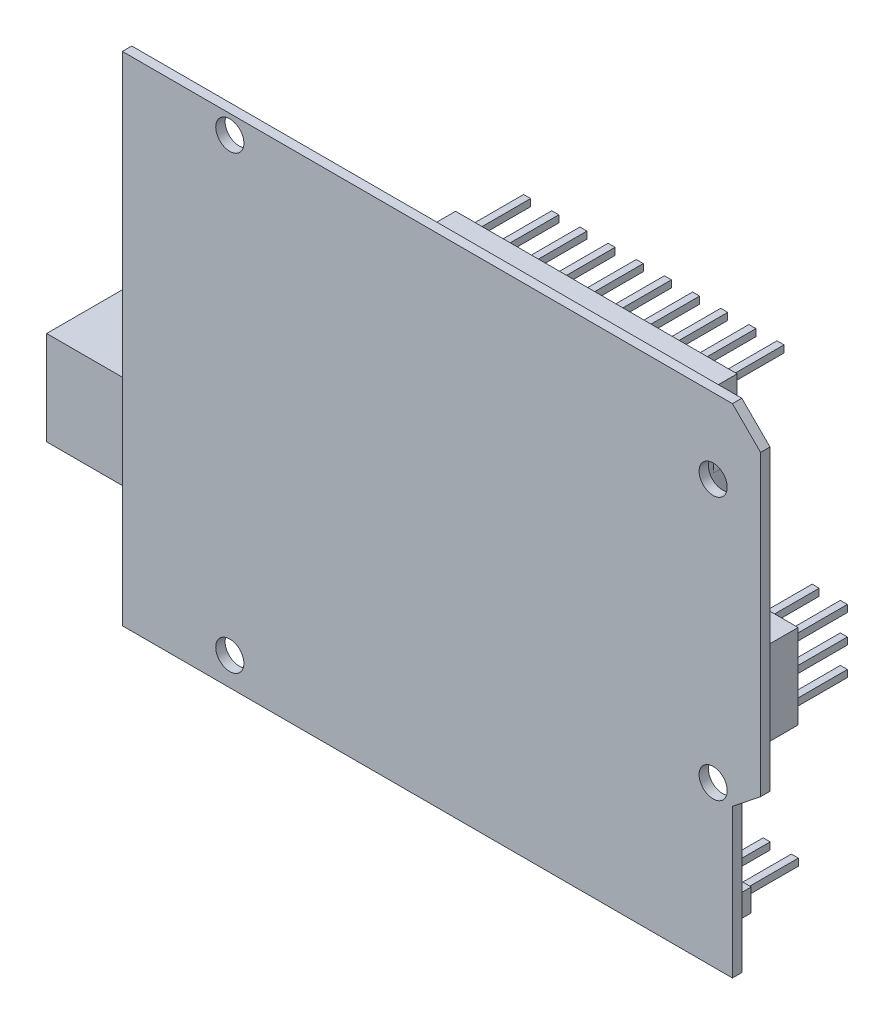
SolidWorks part; units mm, degrees
ref_plane "Front Plane" through (0, 0, 0) normal (0, 0, 1) x (1, 0, 0)
ref_plane "Top Plane" through (0, 0, 0) normal (0, 1, 0) x (1, 0, 0)
ref_plane "Right Plane" through (0, 0, 0) normal (1, 0, 0) x (0, 0, -1)
sketch "Sketch1" plane through (0, 0, 0) normal (0, 0, 1) x (1, 0, 0)
  line L0 (22.754, 124.2709) -> (19.754, 127.2709)
  line L1 (19.754, 74.2709) -> (-45.246, 74.2709)
  line L2 (22.754, 92.5002) -> (22.754, 124.2709)
  line L3 (19.754, 127.2709) -> (-45.246, 127.2709)
  line L4 (-45.246, 74.2709) -> (-45.246, 127.2709)
  line L5 (22.754, 92.5002) -> (19.754, 90.1139)
  line L6 (19.754, 90.1139) -> (19.754, 74.2709)
extrude "Boss-Extrude1" add sketch "Sketch1" against normal blind 1
sketch "Sketch2" plane through (0, 0, -1) normal (0, 0, -1) x (-1, 0, 0)
  line L1 (38.3165, 86.2081) -> (54.3165, 86.2081)
  line L2 (38.3165, 86.2081) -> (38.3165, 96.2081)
  line L3 (38.3165, 96.2081) -> (54.3165, 96.2081)
  line L4 (54.3165, 86.2081) -> (54.3165, 96.2081)
  dimension "D1" = 16
  dimension "D2" = 10
extrude "Boss-Extrude2" add sketch "Sketch2" along normal blind 10
sketch "Sketch3" plane through (-54.3165, 0, 0) normal (-1, 0, 0) x (0, 0, 1)
  line L1 (-8.51, 88.5529) -> (-3.6209, 88.5529)
  line L2 (-8.51, 88.5529) -> (-8.51, 93.9309)
  line L3 (-8.51, 93.9309) -> (-3.6209, 93.9309)
  line L4 (-3.6209, 88.5529) -> (-3.6209, 93.9309)
extrude "Cut-Extrude1" cut sketch "Sketch3" against normal blind 10
sketch "Sketch4" plane through (0, 0, -1) normal (0, 0, -1) x (-1, 0, 0)
  line L0 (45.246, 74.2709) -> (-19.754, 74.2709) construction
  line L1 (-16.754, 76.2709) -> (28.246, 76.2709)
  line L2 (-16.754, 76.2709) -> (-16.754, 78.6709)
  line L3 (-16.754, 78.6709) -> (28.246, 78.6709)
  line L4 (28.246, 76.2709) -> (28.246, 78.6709)
  line L5 (-15.254, 125.2709) -> (14.746, 125.2709)
  line L6 (-15.254, 125.2709) -> (-15.254, 122.8709)
  line L7 (-15.254, 122.8709) -> (14.746, 122.8709)
  line L8 (14.746, 125.2709) -> (14.746, 122.8709)
  line L9 (-19.754, 127.2709) -> (45.246, 127.2709) construction
  line L10 (-22.754, 92.5002) -> (-22.754, 124.2709) construction
  line L11 (-19.754, 74.2709) -> (-19.754, 90.1139) construction
  dimension "D1" = 2.4
  dimension "D2" = 2.4
  dimension "D3" = 2
  dimension "D4" = 2
  dimension "D5" = 7.5
  dimension "D6" = 3
  dimension "D7" = 45
  dimension "D8" = 30
extrude "Boss-Extrude3" add sketch "Sketch4" along normal blind 4
sketch "Sketch5" plane through (0, 0, -1) normal (0, 0, -1) x (-1, 0, 0)
  line L0 (-15.254, 122.8709) -> (14.746, 122.8709) construction
  line L1 (-13.754, 118.3709) -> (21.246, 118.3709)
  line L2 (-13.754, 118.3709) -> (-13.754, 108.3709)
  line L3 (-13.754, 108.3709) -> (21.246, 108.3709)
  line L4 (21.246, 118.3709) -> (21.246, 108.3709)
  line L5 (-22.754, 92.5002) -> (-22.754, 124.2709) construction
  dimension "D1" = 10
  dimension "D2" = 35
  dimension "D3" = 4.5
  dimension "D4" = 9
extrude "Boss-Extrude4" add sketch "Sketch5" along normal blind 7
sketch "Sketch6" plane through (0, 0, -8) normal (0, 0, -1) x (-1, 0, 0)
  line L0 (21.246, 108.3709) -> (21.246, 118.3709) construction
  line L1 (-13.754, 118.3709) -> (21.246, 118.3709)
  line L2 (-13.754, 118.3709) -> (-13.754, 116.8709)
  line L3 (-13.754, 116.8709) -> (21.246, 116.8709)
  line L4 (21.246, 118.3709) -> (21.246, 116.8709)
  line L6 (-13.754, 108.3709) -> (21.246, 108.3709)
  line L7 (-13.754, 108.3709) -> (-13.754, 109.8709)
  line L8 (-13.754, 109.8709) -> (21.246, 109.8709)
  line L9 (21.246, 108.3709) -> (21.246, 109.8709)
  dimension "D1" = 1.5
  dimension "D2" = 1.5
extrude "Cut-Extrude2" cut sketch "Sketch6" against normal blind 4
fillet "Fillet1" radius 1 4 edges at (-21.246, 116.8709, -6) (-21.246, 109.8709, -6) (13.754, 116.8709, -6) (13.754, 109.8709, -6)
sketch "Sketch7" plane through (0, 0, -1) normal (0, 0, -1) x (-1, 0, 0)
  circle A0 centre (-17.7001, 119.2709) radius 1.5
  circle A1 centre (-17.7001, 91.2709) radius 1.5
  circle A2 centre (33.7999, 125.2709) radius 1.5
  circle A3 centre (33.7999, 77.2709) radius 1.5
extrude "Cut-Extrude3" cut sketch "Sketch7" against normal blind 4
sketch "Sketch8" plane through (0, 0, -5) normal (0, 0, -1) x (-1, 0, 0)
  line L0 (-15.254, 124.0709) -> (14.746, 124.0709) construction
  line L1 (-14.254, 124.4459) -> (-13.504, 124.4459)
  line L2 (-14.254, 124.4459) -> (-14.254, 123.6959)
  line L3 (-14.254, 123.6959) -> (-13.504, 123.6959)
  line L4 (-13.504, 124.4459) -> (-13.504, 123.6959)
  line L5 (-15.254, 125.2709) -> (-15.254, 122.8709) construction
  line L6 (14.746, 122.8709) -> (14.746, 125.2709) construction
  dimension "D1" = 0.75
  dimension "D2" = 0.75
  dimension "D3" = 0.375
  dimension "D4" = 1
extrude "Boss-Extrude5" add sketch "Sketch8" along normal blind 6
pattern_linear "LPattern1" count 10 spacing 3 along (-1, 0, 0) of "Boss-Extrude5"
sketch "Sketch9" plane through (0, 0, -5) normal (0, 0, -1) x (-1, 0, 0)
  line L0 (-16.754, 77.4709) -> (28.246, 77.4709) construction
  line L1 (-16.754, 78.6709) -> (-16.754, 76.2709) construction
  line L2 (28.246, 76.2709) -> (28.246, 78.6709) construction
  line L4 (-15.7778, 77.8459) -> (-15.0278, 77.8459)
  line L5 (-15.7778, 77.8459) -> (-15.7778, 77.0959)
  line L6 (-15.7778, 77.0959) -> (-15.0278, 77.0959)
  line L7 (-15.0278, 77.8459) -> (-15.0278, 77.0959)
  dimension "D1" = 0.75
  dimension "D2" = 0.75
  dimension "D3" = 0.375
extrude "Boss-Extrude6" add sketch "Sketch9" along normal blind 6
pattern_linear "LPattern2" count 15 spacing 3 along (-1, 0, 0) of "Boss-Extrude6"
sketch "Sketch10" plane through (0, 0, -1) normal (0, 0, -1) x (-1, 0, 0)
  circle A0 centre (26.5467, 118.215) radius 2.5
  circle A1 centre (31.9407, 118.215) radius 2.5
  dimension "D1" = 5
  dimension "D2" = 5
extrude "Boss-Extrude7" add sketch "Sketch10" along normal blind 6
sketch "Sketch11" plane through (0, 0, -1) normal (0, 0, -1) x (-1, 0, 0)
  line L1 (-21.7492, 96.1139) -> (-16.9492, 96.1139)
  line L2 (-21.7492, 96.1139) -> (-21.7492, 105.1139)
  line L3 (-21.7492, 105.1139) -> (-16.9492, 105.1139)
  line L4 (-16.9492, 96.1139) -> (-16.9492, 105.1139)
  dimension "D1" = 4.8
  dimension "D2" = 9
  dimension "D3" = 6
extrude "Boss-Extrude8" add sketch "Sketch11" along normal up to surface (4 mm away) up to face at (0.254, 124.0709, -5)
sketch "Sketch12" plane through (0, 0, -5) normal (0, 0, -1) x (-1, 0, 0)
  line L0 (-21.7492, 96.1139) -> (-16.9492, 96.1139) construction
  line L1 (-20.9992, 97.8639) -> (-20.2492, 97.8639)
  line L2 (-20.9992, 97.8639) -> (-20.9992, 97.1139)
  line L3 (-20.9992, 97.1139) -> (-20.2492, 97.1139)
  line L4 (-20.2492, 97.8639) -> (-20.2492, 97.1139)
  line L5 (-21.7492, 105.1139) -> (-21.7492, 96.1139) construction
  dimension "D1" = 0.75
  dimension "D2" = 0.75
  dimension "D3" = 1
  dimension "D4" = 0.75
extrude "Boss-Extrude9" add sketch "Sketch12" along normal blind 6
pattern_linear "LPattern3" count 3 spacing 3 along (0, 1, 0) count 2 spacing 3 along (-1, 0, 0) of "Boss-Extrude9"
sketch "Sketch13" plane through (0, 0, -1) normal (0, 0, -1) x (-1, 0, 0)
  line L1 (16.3872, 103.9285) -> (30.5081, 103.9285)
  line L2 (16.3872, 103.9285) -> (16.3872, 99.5659)
  line L3 (16.3872, 99.5659) -> (30.5081, 99.5659)
  line L4 (30.5081, 103.9285) -> (30.5081, 99.5659)
extrude "Boss-Extrude10" add sketch "Sketch13" along normal blind 4
fillet "Fillet2" radius 1 4 edges at (-30.5081, 103.9285, -3) (-30.5081, 99.5659, -3) (-16.3872, 103.9285, -3) (-16.3872, 99.5659, -3)
